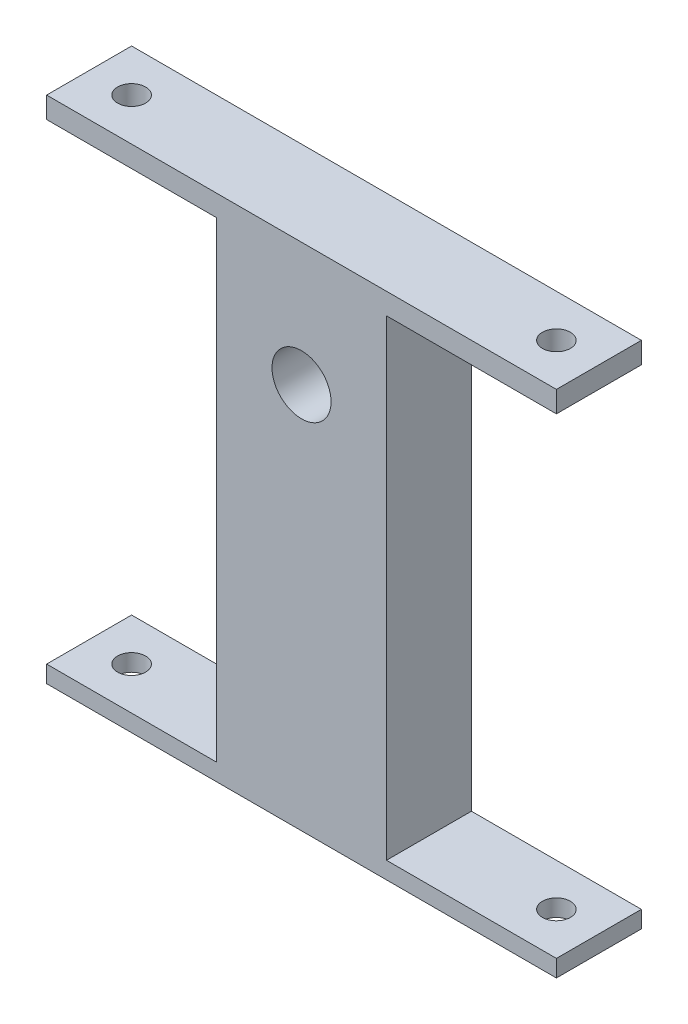
SolidWorks part; units mm, degrees
ref_plane "Front Plane" through (0, 0, 0) normal (0, 0, 1) x (1, 0, 0)
ref_plane "Top Plane" through (0, 0, 0) normal (0, 1, 0) x (1, 0, 0)
ref_plane "Right Plane" through (0, 0, 0) normal (1, 0, 0) x (0, 0, -1)
sketch "Sketch1" plane through (0, 0, 0) normal (0, 0, 1) x (1, 0, 0)
  line L0 (-30, 30) -> (-30, 27.5)
  line L1 (-30, 30) -> (30, 30)
  line L3 (-30, -30) -> (30, -30)
  line L5 (-30, 27.5) -> (-10, 27.5)
  line L6 (-10, 27.5) -> (-10, -28)
  line L7 (-10, -28) -> (-30, -28)
  line L8 (-30, -28) -> (-30, -30)
  line L9 (0, -33) -> (0, 33) construction
  line L10 (30, -28) -> (30, -30)
  line L11 (10, -28) -> (30, -28)
  line L12 (10, 27.5) -> (10, -28)
  line L13 (30, 27.5) -> (10, 27.5)
  line L14 (30, 30) -> (30, 27.5)
  circle A0 centre (0, 15.47) radius 3.475
  point P0 (0, 0)
  dimension "D4" = 6.95
  dimension "D1" = 60
  dimension "D2" = 60
  dimension "D3" = 45.47
  dimension "D5" = 30
  dimension "D6" = 30
  dimension "D7" = 2.5
  dimension "D8" = 2
  dimension "D9" = 10
extrude "Boss-Extrude1" add sketch "Sketch1" along normal blind 10
sketch "Esquisse1" plane through (0, 30, 0) normal (0, 1, 0) x (1, 0, 0)
  line L0 (10, 0) -> (30, 0) construction
  line L2 (-30, -10) -> (-30, 0) construction
  line L3 (-10, 0) -> (-30, 0) construction
  circle A0 centre (25, -5) radius 1.65
  circle A1 centre (-25, -5) radius 1.65
  dimension "D3" = 3.3
  dimension "D4" = 3.3
  dimension "D1" = 5
  dimension "D2" = 5
  dimension "D5" = 5
  dimension "D6" = 5
extrude "Enlèv. mat.-Extru.1" cut sketch "Esquisse1" against normal through all both and the other way through all
